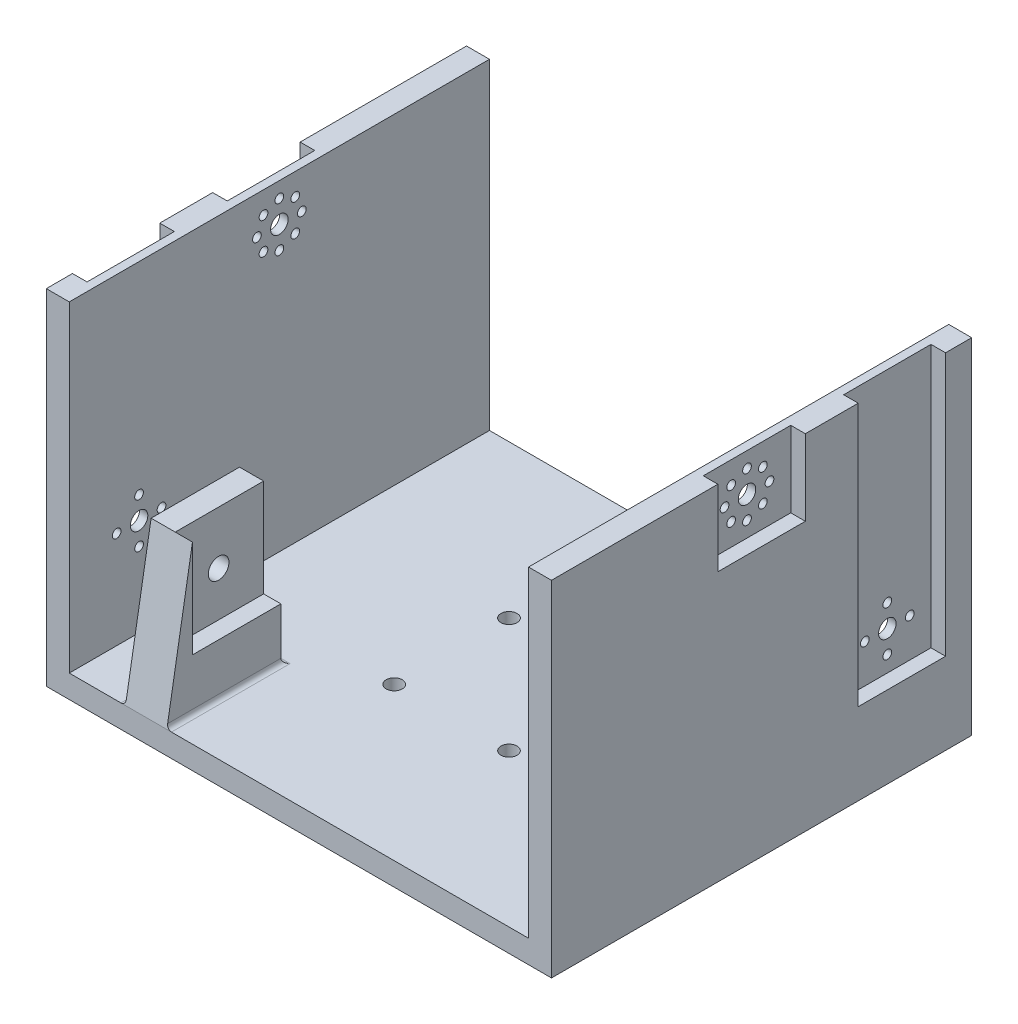
SolidWorks part; units mm, degrees
ref_plane "Front" through (0, 0, 0) normal (0, 0, 1) x (1, 0, 0)
ref_plane "Top" through (0, 0, 0) normal (0, 1, 0) x (1, 0, 0)
ref_plane "Right" through (0, 0, 0) normal (1, 0, 0) x (0, 0, -1)
sketch "Sketch2" plane through (0, 0, 0) normal (0, 1, 0) x (1, 0, 0)
  line L0 (0, 0) -> (0, -91.5) construction
  line L1 (-100, -91.5) -> (100, -91.5)
  line L2 (-100, -91.5) -> (-100, 91.5)
  line L3 (-100, 91.5) -> (100, 91.5)
  line L4 (100, -91.5) -> (100, 91.5)
  line L5 (0, 0) -> (-100, 0) construction
  point P0 (0, 0)
  dimension "D1" = 200
  dimension "D2" = 200
extrude "Boss-Extrude1" add sketch "Sketch2" along normal blind 10
sketch "Sketch3" plane through (0, 0, 0) normal (0, 1, 0) x (1, 0, 0)
  line L0 (-100, -91.5) -> (100, -91.5) construction
  line L1 (-100, 91.5) -> (-110, 91.5)
  line L2 (-100, 91.5) -> (-100, -91.5)
  line L3 (-100, -91.5) -> (-110, -91.5)
  line L4 (-110, 91.5) -> (-110, -91.5)
  line L5 (0, 0) -> (0, 91.5) construction
  line L6 (100, 91.5) -> (-100, 91.5) construction
  line L7 (110, 91.5) -> (110, -91.5)
  line L8 (100, -91.5) -> (110, -91.5)
  line L9 (100, 91.5) -> (100, -91.5)
  line L10 (100, 91.5) -> (110, 91.5)
  dimension "D1" = 10
extrude "Boss-Extrude2" add sketch "Sketch3" along normal blind 150
sketch "Sketch4" plane through (0, 10, 0) normal (0, 1, 0) x (1, 0, 0)
  point P4 (0, 0)
hole_wizard "M6 Clearance Hole1" positions "Sketch5" profile "Sketch6" hole size "M6" standard "ANSI Metric" end condition up to next
sketch "Sketch5" plane through (0, 10, 0) normal (0, 1, 0) x (1, 0, 0)
  line L0 (0, 0) -> (0, 25) construction
  line L1 (0, 25) -> (-25, 25) construction
  line L3 (0, 25) -> (25, 25) construction
  point P0 (-25, 25)
  point P13 (25, 25)
  point P14 (25, -25)
  point P15 (-25, -25)
  dimension "D1" = 25
  dimension "D2" = 4
sketch "Sketch6" plane through (-25, 10, -25) normal (1, 0, 0) x (0, 0, 1)
  line L0 (0, 0) -> (0, 10)
  line L1 (0, 10) -> (3.5, 10)
  line L2 (3.5, 10) -> (3.5, 0)
  line L5 (3.5, 0) -> (0, 0)
  line L11 (0, -6.35) -> (0, 107.95) construction
  dimension "Thru Hole Dia." = 7
  dimension "Thru Hole Depth" = 10
sketch "Sketch7" plane through (100, 0, 0) normal (-1, 0, 0) x (0, 0, 1)
  line L0 (-91.5, 150) -> (91.5, 150) construction
  line L1 (0, 133.49) -> (0, 143.269) construction
  line L2 (0, 133.49) -> (0, 143.269) construction
  circle A0 centre (0, 133.49) radius 3.81
  circle A1 centre (0, 143.269) radius 1.8987
  circle A2 centre (6.9148, 140.4048) radius 1.8987
  circle A3 centre (9.779, 133.49) radius 1.8987
  circle A4 centre (6.9148, 126.5752) radius 1.8987
  circle A5 centre (0, 123.711) radius 1.8987
  circle A6 centre (-6.9148, 126.5752) radius 1.8987
  circle A7 centre (-9.779, 133.49) radius 1.8987
  circle A8 centre (-6.9148, 140.4048) radius 1.8987
  point P7 (0, 150)
  dimension "D1" = 7.62
  dimension "D3" = 3.7973
  dimension "D2" = 16.51
  dimension "D6" = 9.779
  dimension "D5" = 8
extrude "Cut-Extrude1" cut sketch "Sketch7" against normal through all both and the other way through all
sketch "Sketch8" plane through (0, 150, 0) normal (0, 1, 0) x (1, 0, 0)
  line L1 (103.65, -19.05) -> (110, -19.05)
  line L2 (103.65, -19.05) -> (103.65, 19.05)
  line L3 (103.65, 19.05) -> (110, 19.05)
  line L4 (110, -19.05) -> (110, 19.05)
  line L5 (103.65, -19.05) -> (110, 19.05) construction
  line L6 (103.65, 19.05) -> (110, -19.05) construction
  line L9 (110, -91.5) -> (110, 91.5) construction
  line L10 (0, 0) -> (0, 91.5) construction
  line L11 (100, 91.5) -> (-100, 91.5) construction
  line L13 (-103.65, 19.05) -> (-110, -19.05) construction
  line L14 (-103.65, -19.05) -> (-110, 19.05) construction
  line L16 (-110, -19.05) -> (-110, 19.05)
  line L17 (-103.65, 19.05) -> (-110, 19.05)
  line L18 (-103.65, -19.05) -> (-103.65, 19.05)
  line L19 (-103.65, -19.05) -> (-110, -19.05)
  point P0 (106.825, 0)
  point P12 (110, 0)
  point P23 (-106.825, 0)
  dimension "D1" = 38.1
  dimension "D2" = 6.35
extrude "Cut-Extrude2" cut sketch "Sketch8" against normal blind 33.02
sketch "Sketch9" plane through (110, 0, 0) normal (1, 0, 0) x (0, 0, -1)
  line L0 (44.5889, 35.5504) -> (50.6849, 35.5504) construction
  line L2 (80.1089, 69.0884) -> (80.1089, 35.5404)
  line L3 (80.1089, 35.5404) -> (42.0889, 35.5404)
  line L4 (42.0889, 69.0884) -> (42.0889, 35.5404)
  line L5 (80.1089, 69.0884) -> (42.0889, 35.5404) construction
  line L6 (80.1089, 35.5404) -> (42.0889, 69.0884) construction
  line L7 (44.5889, 44.6944) -> (44.5889, 35.5504) construction
  line L13 (80.1089, 69.0884) -> (80.1089, 150)
  line L14 (19.05, 150) -> (91.5, 150) construction
  line L15 (80.1089, 150) -> (42.0889, 150)
  line L16 (42.0889, 150) -> (42.0889, 69.0884)
  point P0 (61.0989, 52.3144)
  point P10 (61.0989, 62.0934)
  point P11 (51.3199, 52.3144)
  point P13 (61.0989, 42.5354)
  point P15 (70.8779, 52.3144)
  dimension "D1" = 0.01
  dimension "D2" = 2.5
extrude "Cut-Extrude3" cut sketch "Sketch9" against normal blind 6.35
sketch "Sketch11" plane through (103.65, 0, 0) normal (1, 0, 0) x (0, 0, -1)
  circle A0 centre (61.0989, 52.3144) radius 3.81
  circle A1 centre (0, 133.49) radius 3.81 construction
extrude "Cut-Extrude4" cut sketch "Sketch11" against normal up to next
hole_wizard "#6 Clearance Hole1" positions "Sketch12" profile "Sketch13" hole size "#6" standard "ANSI Inch" end condition up to next
sketch "Sketch12" plane through (103.65, 0, 0) normal (1, 0, 0) x (0, 0, -1)
  point P0 (61.0989, 62.0934)
  point P3 (51.3199, 52.3144)
  point P6 (70.8779, 52.3144)
  point P10 (61.0989, 42.5354)
sketch "Sketch13" plane through (103.65, 62.0934, -61.0989) normal (0, 1, 0) x (0, 0, -1)
  line L0 (0, 0) -> (0, 3.65)
  line L1 (0, 3.65) -> (1.8986, 3.65)
  line L2 (1.8986, 3.65) -> (1.8986, 0)
  line L5 (1.8986, 0) -> (0, 0)
  line L11 (0, -6.35) -> (0, 107.95) construction
  dimension "Thru Hole Dia." = 3.7973
  dimension "Thru Hole Depth" = 3.65
ref_plane "Plane1" through (0, 0, 0) normal (-0.7071, 0, 0.7071) x (0.7071, 0, 0.7071)
ref_axis "Axis1" through (0, 0, 0) along (0, 1, 0)
pattern_circular "CirPattern1" count 2 over 360 about axis through (0, 0, 0) along (0, 1, 0) of "Cut-Extrude3", "Cut-Extrude4", "#6 Clearance Hole1"
sketch "Esquisse1" plane through (0, 10, 0) normal (0, 1, 0) x (1, 0, 0)
  line L1 (53.59, 80.11) -> (77, 80.11)
  line L2 (53.59, 80.11) -> (53.59, 42.09)
  line L3 (53.59, 42.09) -> (77, 42.09)
  line L4 (77, 80.11) -> (77, 42.09)
  line L5 (110, -91.5) -> (110, 91.5) construction
  line L6 (110, 91.5) -> (-110, 91.5) construction
  point P5 (77, 61.1)
  dimension "D1" = 23.41
  dimension "D2" = 30.4
  dimension "D3" = 38.02
  dimension "D4" = 33
extrude "Boss.-Extru.1" add sketch "Esquisse1" along normal blind 65.1
sketch "Esquisse3" plane through (0, 75.1, 0) normal (0, 1, 0) x (1, 0, 0)
  line L0 (53.59, 42.09) -> (64.59, 42.09)
  line L1 (53.59, 42.09) -> (77, 42.09) construction
  line L2 (64.59, 42.09) -> (64.59, 80.11)
  line L3 (77, 80.11) -> (53.59, 80.11) construction
  line L4 (64.59, 80.11) -> (53.59, 80.11)
  line L5 (53.59, 80.11) -> (53.59, 42.09)
  dimension "D1" = 11
extrude "Enlèv. mat.-Extru.1" cut sketch "Esquisse3" against normal blind 39.56
sketch "Esquisse4" plane through (64.59, 0, 0) normal (-1, 0, 0) x (0, 0, 1)
  circle A0 centre (-61.281, 51.9838) radius 4.5
  dimension "D1" = 9
extrude "Enlèv. mat.-Extru.2" cut sketch "Esquisse4" against normal up to next
sketch "Esquisse5" plane through (0, 10, 0) normal (0, 1, 0) x (1, 0, 0)
  line L1 (77, 42.09) -> (45.0859, 42.09)
  line L2 (77, 42.09) -> (77, 35.7298)
  line L3 (77, 35.7298) -> (45.0859, 35.7298)
  line L4 (45.0859, 42.09) -> (45.0859, 35.7298)
extrude "Boss.-Extru.2" add sketch "Esquisse5" along normal blind 65.26
sketch "Esquisse6" plane through (45.0859, 0, 0) normal (-1, 0, 0) x (0, 0, 1)
  line L0 (-35.7298, 10) -> (-35.7298, 75.26)
  line L1 (-35.7298, 75.26) -> (4.2702, 10)
  line L2 (4.2702, 10) -> (-35.7298, 10)
  dimension "D1" = 40
extrude "Boss.-Extru.3" add sketch "Esquisse6" against normal up to vertex (31.9141 mm away) up to point (77, 75.26, -35.7298)
fillet "Congé4" radius 2 3 edges at (77, 10, -37.9199) (45.0859, 10, -18.9099) (61.0429, 10, 4.2702)
fillet "Congé5" radius 2 1 edges at (53.59, 10, -61.1)
sketch "Esquisse8" plane through (0, 10, 0) normal (0, 1, 0) x (1, 0, 0)
  line L0 (-100, -91.5) -> (100, -91.5) construction
  line L1 (-75.5, -41.85) -> (-57.5, -41.85)
  line L2 (-75.5, -41.85) -> (-75.5, -80.35)
  line L3 (-75.5, -80.35) -> (-57.5, -80.35)
  line L4 (-57.5, -41.85) -> (-57.5, -80.35)
  line L5 (-110, -80.1089) -> (-110, -91.5) construction
  point P4 (-75.5, -61.1)
  dimension "D1" = 30.4
  dimension "D2" = 34.5
  dimension "D3" = 18
  dimension "D4" = 38.5
extrude "Boss.-Extru.4" add sketch "Esquisse8" along normal blind 65.1
sketch "Esquisse9" plane through (0, 75.1, 0) normal (0, 1, 0) x (1, 0, 0)
  line L0 (-57.5, -41.85) -> (-65, -41.85)
  line L1 (-57.5, -41.85) -> (-75.5, -41.85) construction
  line L2 (-65, -41.85) -> (-65, -80.35)
  line L3 (-75.5, -80.35) -> (-57.5, -80.35) construction
  line L4 (-65, -80.35) -> (-57.5, -80.35)
  line L5 (-57.5, -80.35) -> (-57.5, -41.85)
  dimension "D1" = 7.5
extrude "Enlèv. mat.-Extru.4" cut sketch "Esquisse9" against normal blind 42.56
sketch "Esquisse10" plane through (-65, 0, 0) normal (1, 0, 0) x (0, 0, -1)
  circle A0 centre (-61.4583, 52.0176) radius 4.5
  dimension "D1" = 9
extrude "Enlèv. mat.-Extru.5" cut sketch "Esquisse10" against normal up to next
sketch "Esquisse12" plane through (-75.5, 0, 0) normal (-1, 0, 0) x (0, 0, 1)
  line L0 (80.35, 10) -> (80.35, 75.1)
  line L1 (80.35, 75.1) -> (91.5, 10)
  arc A0 (91.5, 10) -> (80.35, 10) centre (85.925, 42.55) cw
  dimension "D1" = 65.1
extrude "Boss.-Extru.5" add sketch "Esquisse12" against normal up to vertex (18 mm away) up to point (-57.5, 10, 80.35)
fillet "Congé6" radius 2 3 edges at (-75.5, 10, 66.675) (-57.5, 10, 66.675) (-66.5, 10, 41.85)
equation "\"Longueur\"= 200"
equation "\"D2@Sketch2\"=\"Longueur\""
equation "\"Largeur\"=200"
equation "\"D1@Sketch2\"=\"Largeur\""
